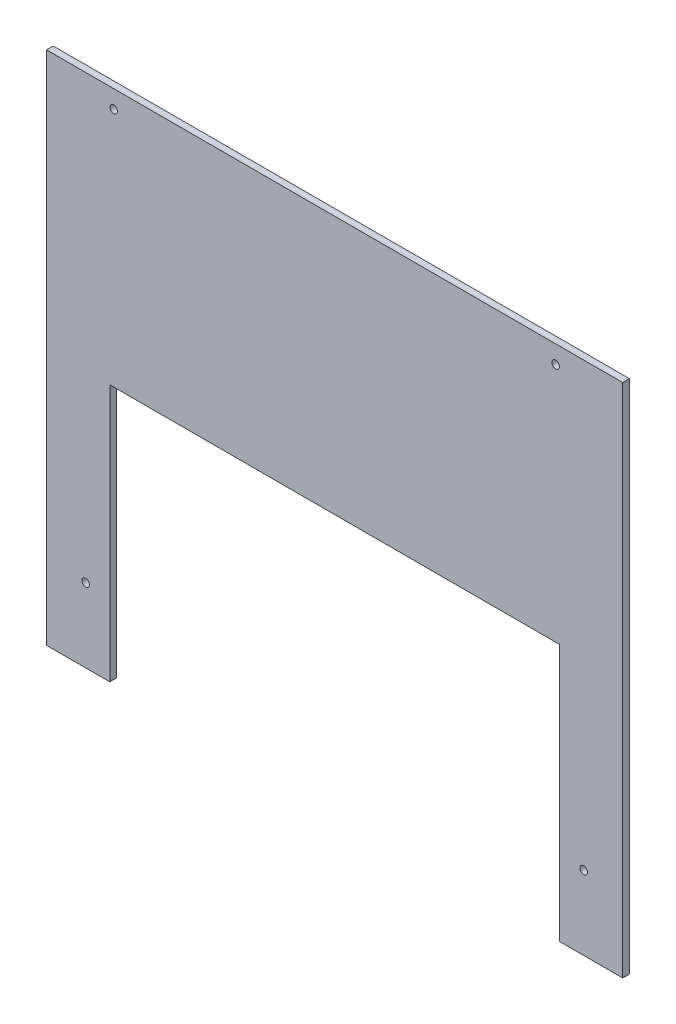
SolidWorks part; units mm, degrees
ref_plane "Plan de face" through (0, 0, 0) normal (0, 0, 1) x (1, 0, 0)
ref_plane "Plan de dessus" through (0, 0, 0) normal (0, 1, 0) x (1, 0, 0)
ref_plane "Plan de droite" through (0, 0, 0) normal (1, 0, 0) x (0, 0, -1)
sketch "Esquisse2" plane through (0, 0, 0) normal (0, 0, 1) x (1, 0, 0)
  line L0 (229.255, -230.48) -> (257.51, -230.48)
  line L1 (0, 0) -> (257.51, 0)
  line L2 (0, 0) -> (0, -230.48)
  line L3 (0, -230.48) -> (28.255, -230.48)
  line L4 (257.51, 0) -> (257.51, -230.48)
  line L6 (28.255, -230.48) -> (28.255, -115.48)
  line L7 (28.255, -115.48) -> (229.255, -115.48)
  line L8 (229.255, -230.48) -> (229.255, -115.48)
  line L9 (30, -8) -> (227.51, -8) construction
  line L10 (17.455, -197.48) -> (240.055, -197.48) construction
  line L11 (128.755, 0) -> (128.755, -197.48) construction
  circle A0 centre (17.455, -197.48) radius 1.7
  circle A1 centre (240.055, -197.48) radius 1.7
  circle A2 centre (227.51, -8) radius 1.7
  circle A3 centre (30, -8) radius 1.7
  point P19 (128.755, -8)
  point P20 (47.5301, -32.871)
  dimension "D1" = 222.6
  dimension "D3" = 3.4
  dimension "D2" = 197.51
  dimension "D4" = 201
  dimension "D5" = 8
  dimension "D6" = 33
  dimension "D7" = 257.51
  dimension "D8" = 230.48
  dimension "D9" = 115
extrude "Boss.-Extru.1" add sketch "Esquisse2" along normal blind 3
